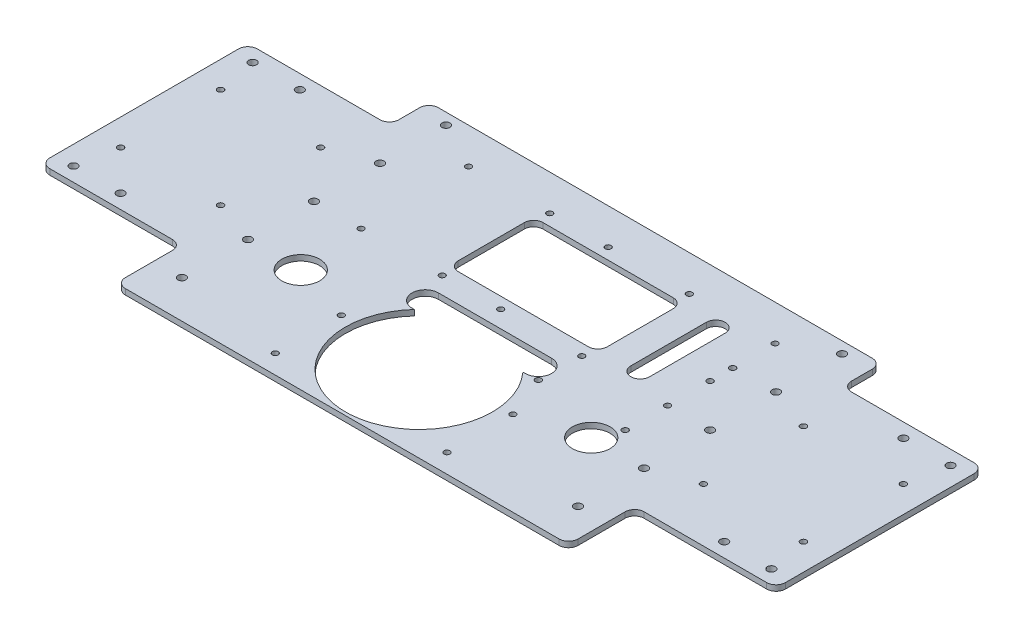
SolidWorks part; units mm, degrees
material "Thornel Mat VMA"
ref_plane "前视基准面" through (0, 0, 0) normal (0, 0, 1) x (1, 0, 0)
ref_plane "上视基准面" through (0, 0, 0) normal (0, 1, 0) x (1, 0, 0)
ref_plane "右视基准面" through (0, 0, 0) normal (1, 0, 0) x (0, 0, -1)
sketch "草图1" plane through (0, 0, 0) normal (0, 1, 0) x (1, 0, 0)
  line L0 (31.5759, -198.8718) -> (31.5759, 46.1282) construction
  line L1 (151.5759, -32.8718) -> (-88.4241, -32.8718)
  line L7 (-88.4241, -198.8718) -> (151.5759, -198.8718)
  line L8 (-88.4241, -198.8718) -> (-88.4241, -32.8718)
  line L10 (151.5759, -198.8718) -> (151.5759, -32.8718)
  line L16 (6.5759, -59.8718) -> (56.5759, -59.8718) construction
  line L18 (6.5759, -34.8718) -> (6.5759, -84.8718) construction
  line L19 (6.5759, -84.8718) -> (56.5759, -84.8718) construction
  line L20 (56.5759, -34.8718) -> (56.5759, -84.8718) construction
  line L21 (151.5759, -94.8718) -> (-88.4241, -94.8718) construction
  line L22 (-88.4241, -49.8718) -> (151.5759, -49.8718) construction
  circle A5 centre (6.5759, -84.8718) radius 1.6 construction
  circle A6 centre (56.5759, -84.8718) radius 1.6 construction
  point P6 (0, -121.2547)
  dimension "D2" = 166
  dimension "D4" = 240
  dimension "D9" = 10
  dimension "D12" = 50
  dimension "D15" = 45
extrude "构型与裁判孔" add sketch "草图1" along normal blind 3 contours L10 L21 L8 L7 region at (31.5759, 0, 115.8718)
sketch "草图4" plane through (0, 3, 0) normal (0, 1, 0) x (1, 0, 0)
  line L0 (-73.4241, -108.8718) -> (-73.4241, -198.8718) construction
  line L1 (77.0759, -32.8718) -> (77.0759, -198.8718) construction
  line L2 (151.5759, -32.8718) -> (-88.4241, -32.8718) construction
  line L3 (-88.4241, -198.8718) -> (-88.4241, -32.8718) construction
  line L4 (31.5759, -32.8718) -> (31.5759, -198.8718) construction
  line L5 (-88.4241, -198.8718) -> (151.5759, -198.8718) construction
  line L6 (-13.9241, -32.8718) -> (-13.9241, -198.8718) construction
  line L7 (-88.4241, -198.8718) -> (151.5759, -198.8718) construction
  line L8 (-88.4241, -198.8718) -> (151.5759, -198.8718) construction
  circle A0 centre (-73.4241, -73.8718) radius 2.1
  circle A1 centre (136.5759, -178.8718) radius 2.1
  circle A2 centre (-73.4241, -108.8718) radius 2.1
  circle A3 centre (-73.4241, -143.8718) radius 2.1
  circle A4 centre (-73.4241, -178.8718) radius 2.1
  circle A5 centre (136.5759, -143.8718) radius 2.1
  circle A6 centre (136.5759, -108.8718) radius 2.1
  circle A7 centre (136.5759, -73.8718) radius 2.1
  circle A8 centre (-73.4241, -38.8718) radius 2.1
  circle A9 centre (136.5759, -38.8718) radius 2.1
  circle A10 centre (77.0759, -188.8718) radius 1.55
  circle A11 centre (-13.9241, -188.8718) radius 1.55
  circle A12 centre (77.0759, -153.8718) radius 1.55
  circle A13 centre (-13.9241, -153.8718) radius 1.55
  dimension "D2" = 20
  dimension "D5" = 35
  dimension "D6" = 35
  dimension "D7" = 35
  dimension "D3" = 4.2
  dimension "D4" = 35
  dimension "D8" = 3.1
  dimension "D9" = 10
  dimension "D10" = 35
  dimension "D1" = 15
  dimension "D11" = 91
extrude "切除-拉伸3" cut sketch "草图4" against normal through all
sketch "草图5" plane through (0, 3, 0) normal (0, 1, 0) x (1, 0, 0)
  line L0 (71.0759, -57.8718) -> (-7.9241, -57.8718)
  line L1 (71.0759, -57.8718) -> (71.0759, -102.8718)
  line L2 (71.0759, -102.8718) -> (-7.9241, -102.8718)
  line L3 (-7.9241, -57.8718) -> (-7.9241, -102.8718)
  line L4 (71.0759, -57.8718) -> (-7.9241, -102.8718) construction
  line L5 (71.0759, -102.8718) -> (-7.9241, -57.8718) construction
  line L6 (31.5759, -32.8718) -> (31.5759, -104.1535) construction
  line L7 (71.0759, -80.3718) -> (-7.9241, -80.3718) construction
  line L8 (31.5759, -57.8718) -> (31.5759, -102.8718) construction
  line L9 (151.5759, -32.8718) -> (-88.4241, -32.8718) construction
  line L10 (91.0759, -100.3718) -> (91.0759, -60.3718) construction
  line L11 (86.0759, -100.3718) -> (86.0759, -60.3718)
  line L12 (96.0759, -100.3718) -> (96.0759, -60.3718)
  line L13 (31.5759, -102.8718) -> (31.5759, -198.8718) construction
  line L16 (-88.4241, -198.8718) -> (151.5759, -198.8718) construction
  line L17 (1.5759, -124.8718) -> (61.5759, -124.8718) construction
  line L18 (1.5759, -117.8718) -> (61.5759, -117.8718)
  line L19 (1.5759, -131.8718) -> (21.5759, -131.8718)
  line L20 (41.5759, -131.8718) -> (61.5759, -131.8718)
  line L21 (-73.4241, -143.8718) -> (136.5759, -143.8718) construction
  circle A0 centre (-5.4241, -51.8718) radius 1.55
  circle A1 centre (68.5759, -51.8718) radius 1.55
  circle A2 centre (68.5759, -108.8718) radius 1.55
  circle A3 centre (-5.4241, -108.8718) radius 1.55
  arc A4 (86.0759, -100.3718) -> (96.0759, -100.3718) centre (91.0759, -100.3718) ccw
  arc A5 (96.0759, -60.3718) -> (86.0759, -60.3718) centre (91.0759, -60.3718) ccw
  arc A8 (1.5759, -117.8718) -> (1.5759, -131.8718) centre (1.5759, -124.8718) ccw
  arc A9 (61.5759, -131.8718) -> (61.5759, -117.8718) centre (61.5759, -124.8718) ccw
  arc A10 (21.5759, -131.8718) -> (41.5759, -131.8718) centre (31.5759, -131.8718) ccw
  circle A11 centre (-45.4241, -143.8718) radius 10
  circle A12 centre (-73.4241, -143.8718) radius 2.1 construction
  circle A13 centre (108.5759, -143.8718) radius 10
  point P1 (110.5236, -62.9669)
  point P23 (91.0759, -80.3718)
  point P33 (31.5759, -124.8718)
  dimension "D3" = 3.1
  dimension "D7" = 5
  dimension "D10" = 7
  dimension "D13" = 20
  dimension "D14" = 28
  dimension "D1" = 79
  dimension "D2" = 45
  dimension "D4" = 37
  dimension "D5" = 28.5
  dimension "D6" = 25
  dimension "D8" = 40
  dimension "D9" = 15
  dimension "D11" = 60
  dimension "D12" = 15
extrude "切除-拉伸4" cut sketch "草图5" against normal through all
sketch "草图9" plane through (0, 0, 0) normal (0, -1, 0) x (1, 0, 0)
  line L0 (-1005.4241, 108.8718) -> (48994.5759, 108.8718) construction
  line L1 (-88.4241, 198.8718) -> (-88.4241, 32.8718) construction
  line L2 (-7.9241, 57.8718) -> (-7.9241, 102.8718) construction
  line L3 (-7.9241, 57.8718) -> (-7.9241, 102.8718) construction
  line L4 (-7.9241, 80.3718) -> (10.0801, 80.3718) construction
  line L5 (-1005.4241, 51.8718) -> (48994.5759, 51.8718) construction
  line L8 (91.0759, 105.3718) -> (91.0759, 78.9227) construction
  circle A0 centre (-5.4241, 108.8718) radius 1.55 construction
  circle A1 centre (-5.4241, 108.8718) radius 1.55 construction
  circle A2 centre (-73.4241, 108.8718) radius 2.1 construction
  circle A3 centre (-73.4241, 108.8718) radius 2.1 construction
  circle A4 centre (68.5759, 108.8718) radius 1.55 construction
  circle A5 centre (68.5759, 108.8718) radius 1.55
  circle A6 centre (-48.4241, 108.8718) radius 1.55
  circle A7 centre (25.5759, 108.8718) radius 1.55
  circle A8 centre (-5.4241, 51.8718) radius 1.55 construction
  circle A9 centre (25.5759, 51.8718) radius 1.55
  circle A10 centre (-48.4241, 51.8718) radius 1.55
  circle A12 centre (114.0759, 51.8718) radius 1.55
  circle A15 centre (68.5759, 51.8718) radius 1.55 construction
  circle A16 centre (114.0759, 74.3718) radius 1.6
  circle A17 centre (136.5759, 38.8718) radius 2.1 construction
  circle A18 centre (114.0759, 86.3718) radius 1.6
  circle A19 centre (114.0759, 108.8718) radius 1.55
  circle A20 centre (114.0759, 131.3718) radius 1.6
  arc A21 (96.0759, 100.3718) -> (86.0759, 100.3718) centre (91.0759, 100.3718) ccw construction
  circle A22 centre (68.0759, 131.3718) radius 1.6
  dimension "D3" = 3.1
  dimension "D5" = 3.1
  dimension "D7" = 3.2
  dimension "D8" = 3.1
  dimension "D9" = 45.5
  dimension "D10" = 22.5
  dimension "D1" = 15
  dimension "D2" = 74
  dimension "D4" = 25
  dimension "D6" = 74
  dimension "D11" = 22.5
sketch "草图6" plane through (0, 0, 0) normal (0, 1, 0) x (1, 0, 0)
  line L0 (-63.0381, -108.8718) -> (146.9619, -108.8718) construction
  line L1 (-88.4241, -53.8718) -> (-163.4241, -53.8718)
  line L2 (-88.4241, -198.8718) -> (-88.4241, -32.8718) construction
  line L3 (-163.4241, -53.8718) -> (-163.4241, -163.8718)
  line L4 (-73.4241, -108.8718) -> (136.5759, -108.8718) construction
  line L5 (-88.4241, -53.8718) -> (-88.4241, -163.8718)
  line L6 (-88.4241, -163.8718) -> (-163.4241, -163.8718)
  line L7 (31.5759, -32.8718) -> (31.5759, -198.8718) construction
  line L8 (151.5759, -32.8718) -> (-88.4241, -32.8718) construction
  line L9 (-88.4241, -198.8718) -> (151.5759, -198.8718) construction
  line L10 (151.5759, -53.8718) -> (151.5759, -163.8718)
  line L11 (151.5759, -163.8718) -> (226.5759, -163.8718)
  line L12 (226.5759, -53.8718) -> (226.5759, -163.8718)
  line L13 (151.5759, -53.8718) -> (226.5759, -53.8718)
  line L14 (-153.4241, -53.8718) -> (-153.4241, -163.8718) construction
  line L15 (-128.4241, -53.8718) -> (-128.4241, -163.8718) construction
  line L16 (-153.4241, -61.3718) -> (-128.4241, -61.3718) construction
  circle A0 centre (-153.4241, -61.3718) radius 2.1
  circle A1 centre (-153.4241, -156.3718) radius 2.1
  circle A2 centre (216.5759, -156.3718) radius 2.1
  circle A3 centre (216.5759, -61.3718) radius 2.1
  circle A4 centre (-128.4241, -61.3718) radius 2.1
  circle A5 centre (-128.4241, -156.3718) radius 2.1
  circle A6 centre (191.5759, -156.3718) radius 2.1
  circle A7 centre (191.5759, -61.3718) radius 2.1
  point P15 (-88.4241, -108.8718)
  point P16 (-163.4241, -108.8718)
  dimension "D4" = 95
  dimension "D6" = 4.2
  dimension "D7" = 4.2
  dimension "D1" = 75
  dimension "D2" = 55
  dimension "D3" = 10
  dimension "D5" = 25
extrude "凸台-拉伸1" add sketch "草图6" along normal blind 3
fillet "圆角1" radius 5 18 edges at (71.0759, 1.5, 102.8718) (-7.9241, 1.5, 102.8718) (-7.9241, 1.5, 57.8718) (71.0759, 1.5, 57.8718) (151.5759, 1.5, 32.8718) (-88.4241, 1.5, 32.8718) (151.5759, 1.5, 53.8718) (151.5759, 1.5, 163.8718) (-88.4241, 1.5, 163.8718) (-88.4241, 1.5, 53.8718) (226.5759, 1.5, 53.8718) (226.5759, 1.5, 163.8718) (151.5759, 1.5, 198.8718) (-88.4241, 1.5, 198.8718) (-163.4241, 1.5, 53.8718) (-163.4241, 1.5, 163.8718) (41.5759, 1.5, 131.8718) (21.5759, 1.5, 131.8718)
sketch "草图7" plane through (0, 3, 0) normal (0, 1, 0) x (1, 0, 0)
  line L0 (146.5759, -32.8718) -> (-83.4241, -32.8718) construction
  line L1 (-48.4241, -32.8718) -> (-48.4241, -82.8718)
  line L2 (-88.4241, -48.8718) -> (-88.4241, -37.8718) construction
  line L3 (-93.4241, -82.8718) -> (-48.4241, -82.8718)
  line L4 (-83.4241, -198.8718) -> (146.5759, -198.8718) construction
  line L5 (31.5759, -198.8718) -> (31.5759, 61.0332) construction
  line L6 (156.5759, -82.8718) -> (111.5759, -82.8718)
  line L7 (151.7733, -149.2908) -> (156.5759, -82.8718)
  line L8 (111.5759, -32.8718) -> (111.5759, -82.8718)
  line L10 (-48.4241, -32.8718) -> (111.5759, -32.8718)
  line L11 (-93.4241, -82.8718) -> (156.5759, -82.8718)
  line L12 (-93.4241, -82.8718) -> (-93.4241, -208.1915)
  line L13 (-93.4241, -208.1915) -> (156.5759, -208.1915)
  line L14 (156.5759, -82.8718) -> (156.5759, -208.1915)
  line L19 (-48.4241, -32.8718) -> (-48.4241, -82.8718)
  line L20 (-48.4241, -82.8718) -> (111.5759, -82.8718)
  line L21 (111.5759, -32.8718) -> (111.5759, -82.8718)
  dimension "D1" = 50
  dimension "D2" = 40
  dimension "D3" = 0
extrude "切除-拉伸5" [suppressed] cut sketch "草图7" against normal blind 10
fillet "圆角2" [suppressed] radius 10
fillet "圆角3" [suppressed] radius 10
sketch "草图8" plane through (0, 3, 0) normal (0, 1, 0) x (1, 0, 0)
  circle A0 centre (31.5759, -158.2052) radius 35.8 construction
  circle A1 centre (31.5759, -158.2052) radius 35.8 construction
  circle A2 centre (31.5759, -158.2052) radius 39
  dimension "D1" = 78
extrude "切除-拉伸6" cut sketch "草图8" against normal blind 10
extrude "切除-拉伸7" cut sketch "草图9" against normal blind 10
sketch "草图10" plane through (0, 0, 0) normal (0, -1, 0) x (1, 0, 0)
  line L0 (-1163.4241, 108.8718) -> (48836.5759, 108.8718) construction
  line L1 (-163.4241, 58.8718) -> (-163.4241, 158.8718) construction
  line L2 (-88.4241, 193.8718) -> (-88.4241, 168.8718) construction
  line L3 (-149.4241, 135.3718) -> (-96.4241, 135.3718) construction
  line L4 (-149.4241, 135.3718) -> (-149.4241, 82.3718) construction
  line L5 (-149.4241, 82.3718) -> (-96.4241, 82.3718) construction
  line L6 (-96.4241, 135.3718) -> (-96.4241, 82.3718) construction
  line L7 (-149.4241, 135.3718) -> (-96.4241, 82.3718) construction
  line L8 (-149.4241, 82.3718) -> (-96.4241, 135.3718) construction
  line L9 (-149.4241, 82.3718) -> (-96.4241, 82.3718) construction
  line L10 (31.5759, 198.8718) -> (31.5759, 131.536) construction
  line L11 (-83.4241, 198.8718) -> (146.5759, 198.8718) construction
  line L12 (212.5759, 82.3718) -> (159.5759, 82.3718) construction
  line L13 (212.5759, 82.3718) -> (159.5759, 135.3718) construction
  line L14 (212.5759, 135.3718) -> (159.5759, 82.3718) construction
  line L15 (159.5759, 135.3718) -> (159.5759, 82.3718) construction
  line L16 (212.5759, 82.3718) -> (159.5759, 82.3718) construction
  line L17 (212.5759, 135.3718) -> (212.5759, 82.3718) construction
  line L18 (212.5759, 135.3718) -> (159.5759, 135.3718) construction
  circle A0 centre (-149.4241, 135.3718) radius 1.6
  circle A1 centre (-96.4241, 135.3718) radius 1.6
  circle A2 centre (-96.4241, 82.3718) radius 1.6
  circle A3 centre (-149.4241, 82.3718) radius 1.6
  circle A4 centre (212.5759, 82.3718) radius 1.6
  circle A5 centre (159.5759, 82.3718) radius 1.6
  circle A6 centre (159.5759, 135.3718) radius 1.6
  circle A7 centre (212.5759, 135.3718) radius 1.6
  point P1 (-122.9241, 108.8718)
  point P5 (-163.4241, 108.8718)
  point P28 (186.0759, 108.8718)
  dimension "D4" = 3.2
  dimension "D5" = 3.2
  dimension "D1" = 8
  dimension "D2" = 53
  dimension "D3" = 53
extrude "切除-拉伸8" cut sketch "草图10" against normal blind 10
